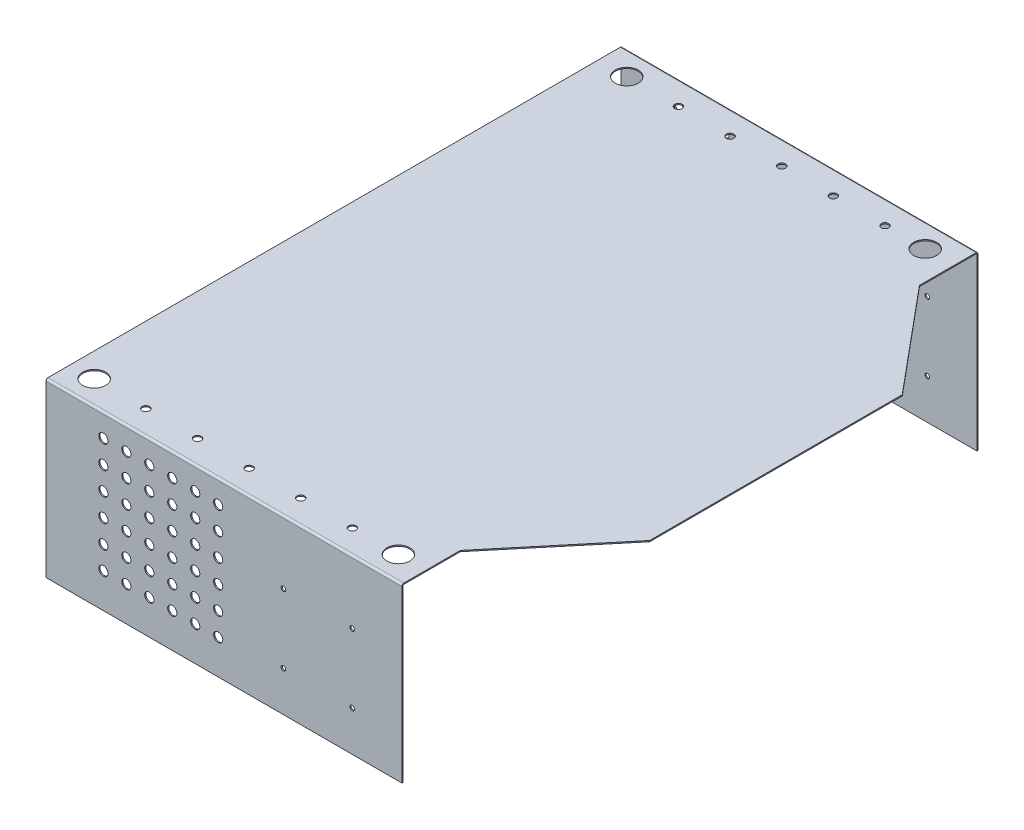
SolidWorks part; units mm, degrees
note: The reader was unsure of these and kept them because the rebuilt part matched: flange length of "Edge-Flange1".
material "1023 Carbon Steel Sheet (SS)"
ref_plane "Front Plane" through (0, 0, 0) normal (0, 0, 1) x (1, 0, 0)
ref_plane "Top Plane" through (0, 0, 0) normal (0, 1, 0) x (1, 0, 0)
ref_plane "Right Plane" through (0, 0, 0) normal (1, 0, 0) x (0, 0, -1)
sketch "Sketch6" plane through (0, 0, 0) normal (0, 1, 0) x (1, 0, 0)
  line L0 (-188.3728, 230.2607) -> (-188.3728, -269.7393)
  line L1 (-188.3728, 230.2607) -> (121.6272, 230.2607)
  line L2 (-188.3728, -269.7393) -> (121.6272, -269.7393)
  line L3 (121.6272, 230.2607) -> (121.6272, 180.2607)
  line L4 (121.6272, -269.7393) -> (121.6272, -219.7393)
  line L5 (196.6272, -129.7393) -> (196.6272, 90.2607)
  line L6 (121.6272, 180.2607) -> (196.6272, 90.2607)
  line L7 (196.6272, -129.7393) -> (121.6272, -219.7393)
  circle A0 centre (-163.3728, 210.2607) radius 10
  circle A1 centre (-118.3728, 210.2607) radius 3.25
  circle A2 centre (-73.3728, 210.2607) radius 3.25
  circle A3 centre (-28.3728, 210.2607) radius 3.25
  circle A4 centre (16.6272, 210.2607) radius 3.25
  circle A6 centre (61.6272, 210.2607) radius 3.25 [skipped]
  circle A7 centre (96.6272, 210.2607) radius 10
  circle A8 centre (61.6272, 210.2607) radius 3.25
  circle A9 centre (-167.3567, -249.7393) radius 10
  circle A10 centre (-122.3567, -249.7393) radius 3.25
  circle A11 centre (-77.3567, -249.7393) radius 3.25
  circle A12 centre (-32.3567, -249.7393) radius 3.25
  circle A13 centre (12.6433, -249.7393) radius 3.25
  circle A14 centre (97.6433, -249.7393) radius 10
  circle A15 centre (57.6433, -249.7393) radius 3.25
  point P3 (-188.3728, -19.7393)
  point P10 (196.6272, -19.7393)
  dimension "D7" = 20
  dimension "D9" = 6.5
  dimension "D14" = 20
  dimension "D1" = 310
  dimension "D2" = 310
  dimension "D3" = 75
  dimension "D4" = 50
  dimension "D5" = 50
  dimension "D6" = 500
  dimension "D8" = 25
  dimension "D10" = 20
  dimension "D11" = 20
  dimension "D12" = 45
  dimension "D15" = 25
  dimension "D16" = 2
  dimension "D17" = 220
  dimension "D18" = 90
  dimension "D19" = 90
  dimension "D13" = 5
base flange "Base-Flange2" sketch "Sketch6" thickness 1 reverse thickness direction no parameters "D1"=0.7366
edge flange "Edge-Flange1" sketch "Sketch17" flange angle 90 flange length 150 flange position material outside bend radius 0.7366 thickness 1 relief rectangular parameters "D6"=10, "D8"=0.2
sketch "Sketch17" plane through (0, -1, 269.7393) normal (0, 0, 1) x (-1, 0, 0)
  line L2 (-121.6272, 0) -> (-121.6272, 149)
  line L3 (-121.6272, 149) -> (188.3728, 149)
  line L4 (188.3728, 149) -> (188.3728, 0)
  line L7 (188.3728, 0) -> (-121.6272, 0) construction
  line L8 (188.3728, 0) -> (-121.6272, 0)
bend "EdgeBend1" bend radius 0.7366 bend angle 90 parameters "D5"=1
sketch "Sketch23" plane through (0, 0, 270.7393) normal (0, 0, 1) x (1, 0, 0)
  line L0 (-188.3728, -1.7366) -> (-188.3728, -150) construction
  line L1 (-188.3728, -150) -> (121.6272, -150) construction
  circle A0 centre (-138.3728, -120) radius 4
  circle A1 centre (-118.3728, -120) radius 4
  circle A2 centre (-98.3728, -120) radius 4
  circle A3 centre (-78.3728, -120) radius 4
  circle A4 centre (-58.3728, -120) radius 4
  circle A5 centre (-38.3728, -120) radius 4
  circle A6 centre (-118.3728, -100) radius 4
  circle A7 centre (-98.3728, -100) radius 4
  circle A8 centre (-78.3728, -100) radius 4
  circle A9 centre (-58.3728, -100) radius 4
  circle A10 centre (-38.3728, -100) radius 4
  circle A11 centre (-118.3728, -80) radius 4
  circle A12 centre (-98.3728, -80) radius 4
  circle A13 centre (-78.3728, -80) radius 4
  circle A14 centre (-58.3728, -80) radius 4
  circle A15 centre (-38.3728, -80) radius 4
  circle A16 centre (-118.3728, -60) radius 4
  circle A17 centre (-98.3728, -60) radius 4
  circle A18 centre (-78.3728, -60) radius 4
  circle A19 centre (-58.3728, -60) radius 4
  circle A20 centre (-38.3728, -60) radius 4
  circle A21 centre (-118.3728, -40) radius 4
  circle A22 centre (-98.3728, -40) radius 4
  circle A23 centre (-78.3728, -40) radius 4
  circle A24 centre (-58.3728, -40) radius 4
  circle A25 centre (-38.3728, -40) radius 4
  circle A26 centre (-118.3728, -20) radius 4
  circle A27 centre (-98.3728, -20) radius 4
  circle A28 centre (-78.3728, -20) radius 4
  circle A29 centre (-58.3728, -20) radius 4
  circle A30 centre (-38.3728, -20) radius 4
  circle A31 centre (-138.3728, -100) radius 4
  circle A32 centre (-138.3728, -80) radius 4
  circle A33 centre (-138.3728, -60) radius 4
  circle A34 centre (-138.3728, -40) radius 4
  circle A35 centre (-138.3728, -20) radius 4
  dimension "D1" = 8
  dimension "D2" = 50
  dimension "D3" = 30
  dimension "D6" = 20
  dimension "D7" = 20
  dimension "D4" = 6
  dimension "D5" = 6
extrude "Cut-Extrude1" cut sketch "Sketch23" against normal blind 10 normal cut yes
sketch "Sketch24" plane through (0, 0, 270.7393) normal (0, 0, 1) x (1, 0, 0)
  line L0 (-188.3728, -150) -> (121.6272, -150) construction
  line L7 (48.4849, -85) -> (106.1727, -85) construction
  circle A0 centre (18.4849, -55) radius 2
  circle A1 centre (78.4849, -55) radius 2
  circle A2 centre (78.4849, -115) radius 2
  circle A3 centre (18.4849, -115) radius 2
  point P0 (48.4849, -75)
  dimension "D4" = 4
  dimension "D1" = 60
  dimension "D2" = 60
  dimension "D3" = 75
extrude "Cut-Extrude2" cut sketch "Sketch24" against normal blind 10 normal cut yes
ref_plane "Plane1" through (0, 0, 19.7393) normal (0, 0, -1) x (-1, 0, 0)
mirror "Mirror2" about plane through (0, 0, 19.7393) normal (0, 0, -1) of "Cut-Extrude1", "Edge-Flange1"
bend "MirrorBend2" bend radius 0.7366 bend angle 90 parameters "D5"=2
mirror "Mirror3" about plane through (0, 0, 19.7393) normal (0, 0, -1) of "Cut-Extrude2"
sketch "Bend-Lines3" [suppressed] plane through (0, 0, 0) normal (0, 1, 0) x (1, 0, 0)
sketch "Bounding-Box3" [suppressed] plane through (0, 0, 0) normal (0, 1, 0) x (1, 0, 0)
sheet metal parameters "Sheet-Metal2" thickness 1 parameters "D1"=0.7366
flat pattern "Flat-Pattern2" [suppressed]
sketch "Bend-Lines4" plane through (0, 0, 0) normal (0, 1, 0) x (1, 0, 0)
sketch3d "Bounding-Box4" [suppressed]
  line L0 (187.3567, 230.2607, 0) -> (187.3567, -269.7393, 0) construction
  line L1 (-197.6433, 230.2607, 0) -> (-197.6433, -269.7393, 0) construction
  line L2 (187.3567, 230.2607, 0) -> (-197.6433, 230.2607, 0) construction
  line L3 (187.3567, -269.7393, 0) -> (-197.6433, -269.7393, 0) construction
sheet metal parameters "Sheet-Metal3" thickness 1 parameters "D1"=0.7366
flat pattern "Flat-Pattern2"
sketch "Bend-Lines4" plane through (0, 0, 0) normal (0, 1, 0) x (1, 0, 0)
  line L0 (122.6433, 230.4954) -> (-187.3567, 230.4954) construction
  line L1 (-187.3567, -269.9739) -> (122.6433, -269.9739) construction
  line L2 (122.6433, 230.4954) -> (-187.3567, 230.4954) construction
  line L3 (-187.3567, -269.9739) -> (122.6433, -269.9739) construction
sketch3d "Bounding-Box4" [suppressed]
  line L0 (-187.3567, 389.73, 0) -> (-187.3567, -429.2085, 0) construction
  line L1 (197.6433, 389.73, 0) -> (197.6433, -429.2085, 0) construction
  line L2 (-187.3567, 389.73, 0) -> (197.6433, 389.73, 0) construction
  line L3 (-187.3567, -429.2085, 0) -> (197.6433, -429.2085, 0) construction
bend of the flat pattern "Flatten-<EdgeBend1>1"
sheet metal parameters "Sheet-Metal4" thickness 1 parameters "D1"=0.7366
flat pattern "Flat-Pattern2"
sketch "Bend-Lines4" plane through (0, 0, 0) normal (0, 1, 0) x (1, 0, 0)
  line L0 (122.6433, 230.4954) -> (-187.3567, 230.4954) construction
  line L1 (-187.3567, -269.9739) -> (122.6433, -269.9739) construction
  line L2 (122.6433, 230.4954) -> (-187.3567, 230.4954) construction
  line L3 (-187.3567, -269.9739) -> (122.6433, -269.9739) construction
sketch3d "Bounding-Box4" [suppressed]
  line L0 (-187.3567, 389.73, 0) -> (-187.3567, -429.2085, 0) construction
  line L1 (197.6433, 389.73, 0) -> (197.6433, -429.2085, 0) construction
  line L2 (-187.3567, 389.73, 0) -> (197.6433, 389.73, 0) construction
  line L3 (-187.3567, -429.2085, 0) -> (197.6433, -429.2085, 0) construction
bend of the flat pattern "Flatten-<EdgeBend1>1"
sheet metal parameters "Sheet-Metal5" thickness 1 parameters "D1"=0.7366
flat pattern "Flat-Pattern2"
sketch "Bend-Lines4" plane through (0, 0, 0) normal (0, 1, 0) x (1, 0, 0)
  line L1 (-188.3728, -269.9739) -> (121.6272, -269.9739) construction
  line L3 (-188.3728, -269.9739) -> (121.6272, -269.9739) construction
sketch3d "Bounding-Box4" [suppressed]
  line L0 (-188.3728, 230.2607, 0) -> (-188.3728, -419.2085, 0) construction
  line L1 (196.6272, 230.2607, 0) -> (196.6272, -419.2085, 0) construction
  line L2 (-188.3728, 230.2607, 0) -> (196.6272, 230.2607, 0) construction
  line L3 (-188.3728, -419.2085, 0) -> (196.6272, -419.2085, 0) construction
bend of the flat pattern "Flatten-<EdgeBend1>1"
sheet metal parameters "Sheet-Metal12" thickness 1 parameters "D1"=0.7366
flat pattern "Flat-Pattern2"
sketch "Bend-Lines4" plane through (0, 0, 0) normal (0, 1, 0) x (1, 0, 0)
  line L0 (121.6272, 230.4954) -> (-188.3728, 230.4954) construction
  line L1 (-188.3728, -269.9739) -> (121.6272, -269.9739) construction
  line L2 (121.6272, 230.4954) -> (-188.3728, 230.4954) construction
  line L3 (-188.3728, -269.9739) -> (121.6272, -269.9739) construction
sketch3d "Bounding-Box4" [suppressed]
  line L0 (-188.3728, 379.73, 0) -> (-188.3728, -419.2085, 0) construction
  line L1 (196.6272, 379.73, 0) -> (196.6272, -419.2085, 0) construction
  line L2 (-188.3728, 379.73, 0) -> (196.6272, 379.73, 0) construction
  line L3 (-188.3728, -419.2085, 0) -> (196.6272, -419.2085, 0) construction
bend of the flat pattern "Flatten-<EdgeBend1>1"
bend of the flat pattern "Flatten-<MirrorBend2>1"
sheet metal parameters "Sheet-Metal13" thickness 1 parameters "D1"=0.7366
flat pattern "Flat-Pattern2"
sketch "Bend-Lines4" plane through (0, 0, 0) normal (0, 1, 0) x (1, 0, 0)
  line L0 (121.6272, 230.4954) -> (-188.3728, 230.4954) construction
  line L1 (-188.3728, -269.9739) -> (121.6272, -269.9739) construction
  line L2 (121.6272, 230.4954) -> (-188.3728, 230.4954) construction
  line L3 (-188.3728, -269.9739) -> (121.6272, -269.9739) construction
sketch3d "Bounding-Box4" [suppressed]
  line L0 (-188.3728, 379.73, 0) -> (-188.3728, -419.2085, 0) construction
  line L1 (196.6272, 379.73, 0) -> (196.6272, -419.2085, 0) construction
  line L2 (-188.3728, 379.73, 0) -> (196.6272, 379.73, 0) construction
  line L3 (-188.3728, -419.2085, 0) -> (196.6272, -419.2085, 0) construction
bend of the flat pattern "Flatten-<EdgeBend1>1"
bend of the flat pattern "Flatten-<MirrorBend2>1"
